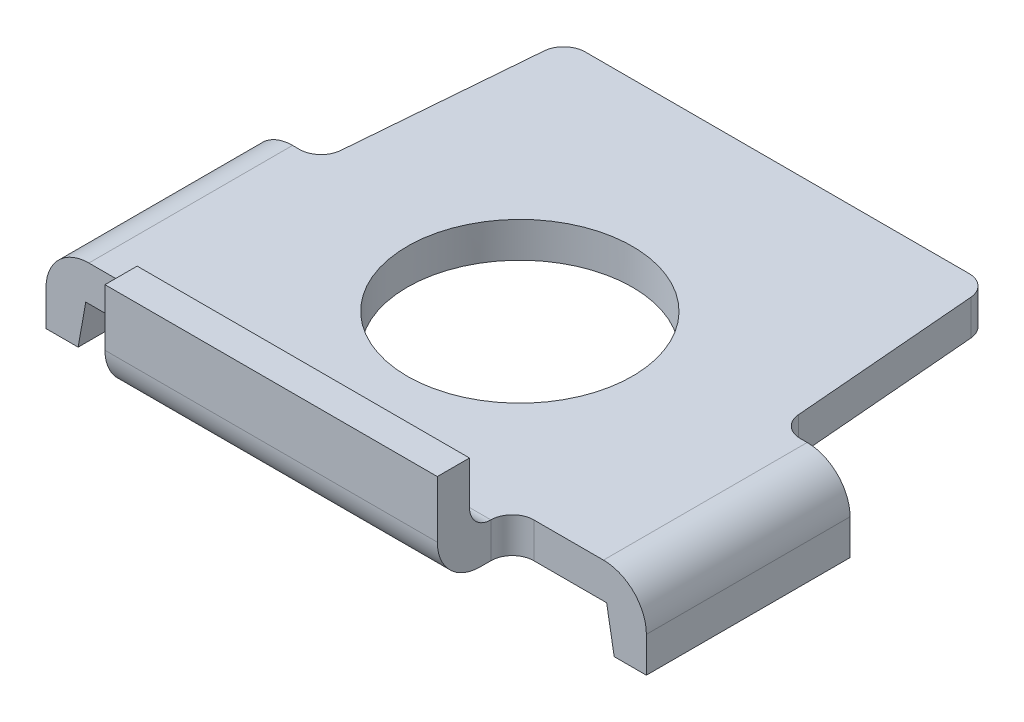
SolidWorks part; units mm, degrees
ref_plane "Plano frontal" through (0, 0, 0) normal (0, 0, 1) x (1, 0, 0)
ref_plane "Plano superior" through (0, 0, 0) normal (0, 1, 0) x (1, 0, 0)
ref_plane "Plano direito" through (0, 0, 0) normal (1, 0, 0) x (0, 0, -1)
sketch "Esboço1" plane through (0, 0, 0) normal (0, 1, 0) x (1, 0, 0)
  line L0 (0, 0) -> (0, 2.1009) construction
  line L1 (-9.875, 2.1009) -> (9.875, 2.1009)
  line L2 (9.875, 2.1009) -> (10.75, -8.4991)
  line L3 (10.75, -8.4991) -> (14, -8.4991)
  line L4 (14, -8.4991) -> (14, -17.9991)
  line L5 (14, -17.9991) -> (7.75, -17.9991)
  line L6 (7.75, -17.9991) -> (7.75, -21.4991)
  line L7 (7.75, -21.4991) -> (-7.75, -21.4991)
  line L8 (-7.75, -17.9991) -> (-7.75, -21.4991)
  line L9 (-14, -17.9991) -> (-7.75, -17.9991)
  line L10 (-14, -8.4991) -> (-14, -17.9991)
  line L11 (-10.75, -8.4991) -> (-14, -8.4991)
  line L12 (-9.875, 2.1009) -> (-10.75, -8.4991)
  point P12 (0, -21.4991)
  dimension "D1" = 19.75
  dimension "D2" = 28
  dimension "D3" = 21.5
  dimension "D4" = 10.6
  dimension "D5" = 9.5
  dimension "D6" = 15.5
  dimension "D7" = 3.5
extrude "Ressalto-extrusão1" add sketch "Esboço1" along normal blind 1.65
sketch "Esboço2" plane through (0, 1.65, 0) normal (0, 1, 0) x (1, 0, 0)
  line L0 (7.75, -21.4991) -> (7.75, -17.9991) construction
  line L1 (-7.75, -21.4991) -> (7.75, -21.4991)
  line L2 (-7.75, -21.4991) -> (-7.75, -19.9991)
  line L3 (-7.75, -19.9991) -> (7.75, -19.9991)
  line L4 (7.75, -21.4991) -> (7.75, -19.9991)
  dimension "D1" = 1.5
extrude "Ressalto-extrusão2" add sketch "Esboço2" along normal blind 3
sketch "Esboço3" plane through (0, 0, 0) normal (0, -1, 0) x (1, 0, 0)
  line L0 (-10.75, 8.4991) -> (-14, 8.4991) construction
  line L1 (-14, 17.9991) -> (-12.5, 17.9991)
  line L2 (-14, 17.9991) -> (-14, 8.4991)
  line L3 (-14, 8.4991) -> (-12.5, 8.4991)
  line L4 (-12.5, 17.9991) -> (-12.5, 8.4991)
  line L5 (14, 8.4991) -> (10.75, 8.4991) construction
  line L6 (14, 17.9991) -> (12.5, 17.9991)
  line L7 (14, 17.9991) -> (14, 8.4991)
  line L8 (14, 8.4991) -> (12.5, 8.4991)
  line L9 (12.5, 17.9991) -> (12.5, 8.4991)
  dimension "D1" = 1.5
  dimension "D2" = 1.5
extrude "Ressalto-extrusão3" add sketch "Esboço3" along normal blind 2
sketch "Esboço4" plane through (0, 1.65, 0) normal (0, 1, 0) x (1, 0, 0)
  line L0 (0, 2.1009) -> (0, -9.8991) construction
  line L1 (9.875, 2.1009) -> (-9.875, 2.1009) construction
  circle A0 centre (0, -9.8991) radius 5.25
  dimension "D2" = 10.5
  dimension "D1" = 12
extrude "Corte-extrusão1" cut sketch "Esboço4" against normal through all
fillet "Filete1" radius 2 2 edges at (14, 1.65, 13.2491) (-14, 1.65, 13.2491)
chamfer "Chanfro1" distance 2 angle 10 2 edges at (12.5, 0, 13.2491)
fillet "Filete3" radius 2 1 edges at (0, 0, 21.4991)
fillet "Filete4" radius 1 1 edges
fillet "Filete5" radius 1 1 edges at (-9.875, 0.825, -2.1009)
fillet "Filete6" radius 1 1 edges at (9.875, 0.825, -2.1009)
fillet "Filete7" radius 1 4 edges at (-10.75, 0.825, 8.4991) (-7.75, 0.825, 17.9991) (7.75, 0.825, 17.9991) (10.75, 0.825, 8.4991)
